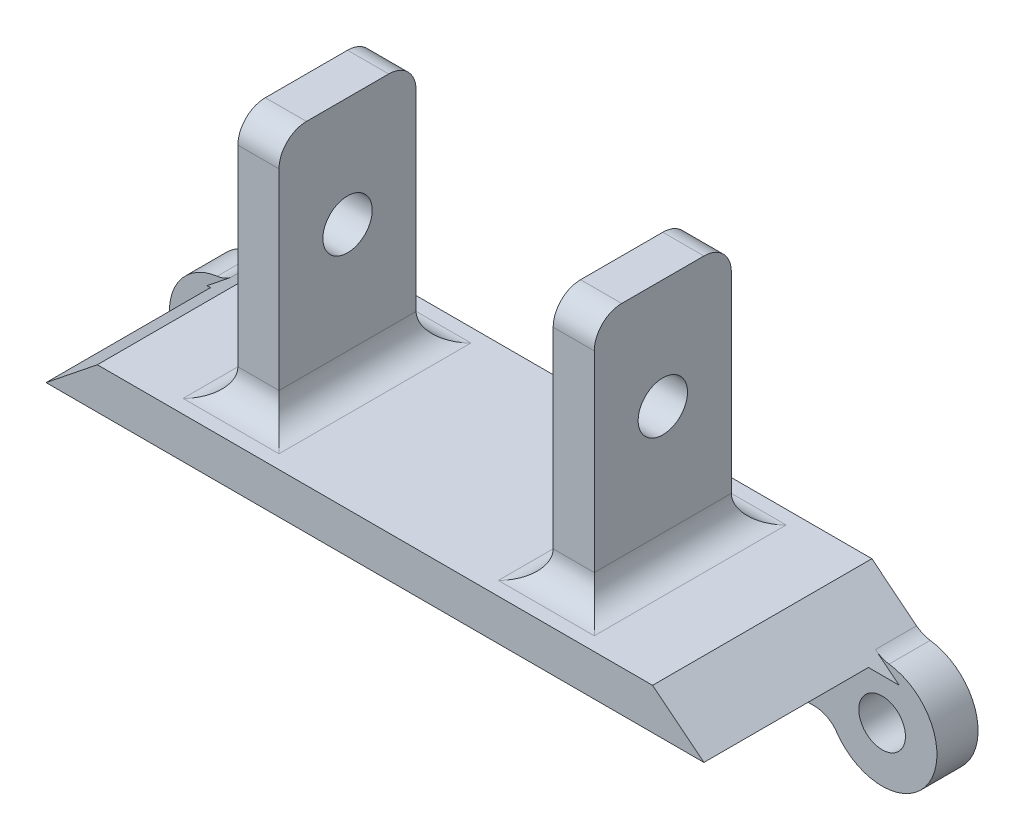
SolidWorks part; units mm, degrees
ref_plane "Спереди" through (0, 0, 0) normal (0, 0, 1) x (1, 0, 0)
ref_plane "Сверху" through (0, 0, 0) normal (0, 1, 0) x (1, 0, 0)
ref_plane "Справа" through (0, 0, 0) normal (1, 0, 0) x (0, 0, -1)
sketch "Эскиз1" plane through (0, 0, 0) normal (0, 0, 1) x (1, 0, 0)
  line L1 (3.7461, -1.4023) -> (44.2539, -1.4023)
  line L6 (44.2539, 7) -> (3.7461, 7)
  line L7 (3.7461, 7) -> (0, 4)
  line L8 (44.2539, 7) -> (48, 4)
  circle A0 centre (0, 0) radius 1.7
  circle A1 centre (48, 0) radius 1.7
  arc A2 (0, 4) -> (3.7461, -1.4023) centre (0, 0) ccw
  arc A3 (44.2539, -1.4023) -> (48, 4) centre (48, 0) ccw
extrude "Бобышка-Вытянуть1" add sketch "Эскиз1" along normal blind 3
sketch "Эскиз2" plane through (0, 0, 3) normal (0, 0, 1) x (1, 0, 0)
  line L0 (0, 4) -> (48, 4)
  line L1 (48, 4) -> (44.2539, 7)
  line L2 (44.2539, 7) -> (3.7461, 7)
  line L3 (44.2539, 7) -> (3.7461, 7) construction
  line L4 (3.7461, 7) -> (0, 4) construction
  line L5 (3.7461, 7) -> (0, 4)
  arc A0 (44.2539, -1.4023) -> (48, 4) centre (48, 0) ccw construction
extrude "Бобышка-Вытянуть2" add sketch "Эскиз2" along normal blind 13
sketch "Эскиз4" plane through (0, 7, 0) normal (0, 1, 0) x (1, 0, 0)
  line L0 (24, 0) -> (24, -16)
  line L1 (44.2539, 0) -> (3.7461, 0) construction
  line L2 (44.2539, -16) -> (3.7461, -16) construction
  line L3 (24, -8) -> (14, -8)
  line L4 (14, -8) -> (14, -3)
  line L5 (14, -3) -> (11, -3)
  line L6 (11, -3) -> (11, -13)
  line L7 (11, -13) -> (14, -13)
  line L8 (14, -13) -> (14, -8)
  line L9 (37, -13) -> (34, -13)
  line L10 (34, -13) -> (34, -8)
  line L11 (34, -3) -> (37, -3)
  line L12 (37, -3) -> (37, -13)
  line L13 (34, -8) -> (34, -3)
extrude "Бобышка-Вытянуть3" add sketch "Эскиз4" along normal blind 18 contours L7 L8 L4 L5 L6 | L13 L10 L9 L12 L11 region at (12.5, 7, 8) region at (35.5, 7, 8)
sketch "Эскиз5" plane through (11, 0, 0) normal (-1, 0, 0) x (0, 0, 1)
  line L0 (8, 7) -> (8, 17)
  line L1 (3, 7) -> (13, 7) construction
  circle A0 centre (8, 17) radius 1.8
extrude "Вырез-Вытянуть1" cut sketch "Эскиз5" against normal blind 34 contours A0 region at (11, 15.7632, 9.2368)
fillet "Скругление1" radius 2 12 edges at (37, 7, 8) (35.5, 7, 3) (34, 7, 8) (14, 7, 8) (35.5, 7, 13) (12.5, 7, 13) (11, 7, 8) (12.5, 7, 3) (12.5, 25, 3) (35.5, 25, 3) (35.5, 25, 13) (12.5, 25, 13)
chamfer "Фаска1" distance 1 angle 45 1 edges at (24, 4, 3)
fillet "Скругление2" radius 2 4 edges at (44.2539, -1.4023, 1.5) (3.7461, -1.4023, 1.5) (0, 4, 1.5) (48, 4, 1.5)
